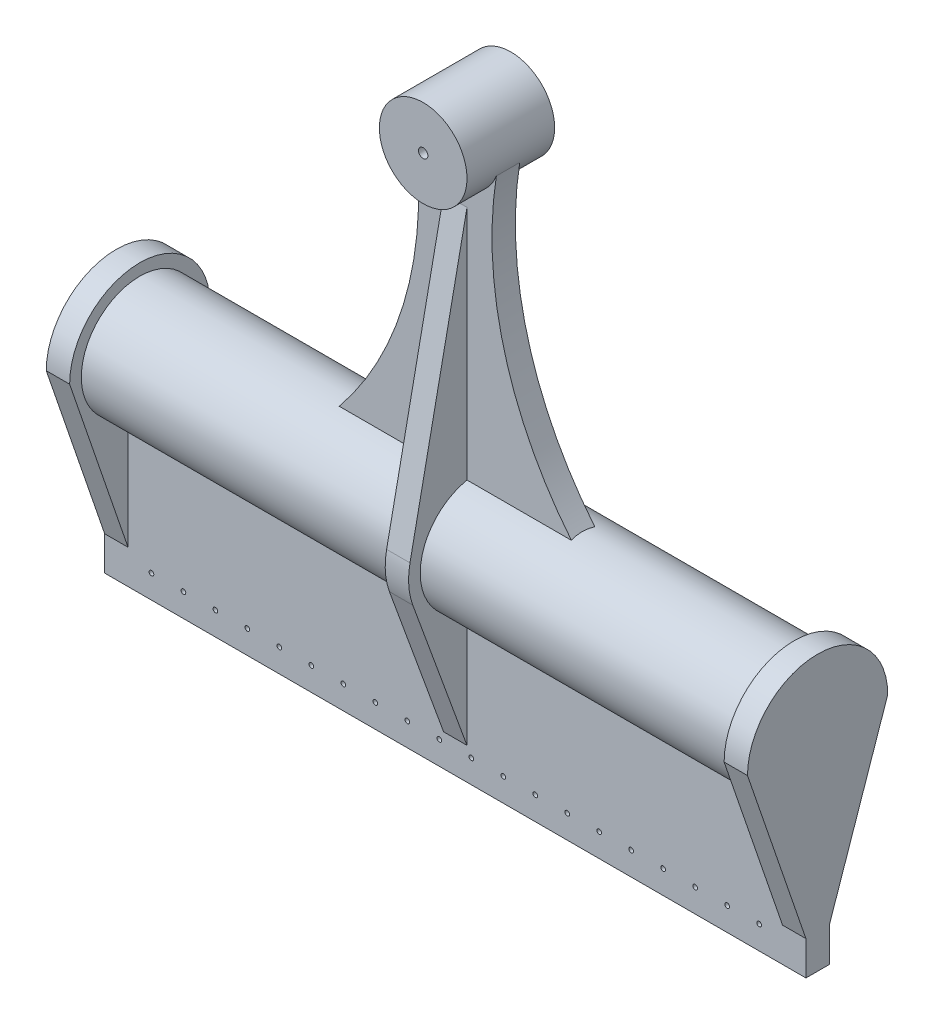
SolidWorks part; units mm, degrees
ref_plane "Front Plane" through (0, 0, 0) normal (1, 0, 0) x (0, 1, 0)
ref_plane "Top Plane" through (0, 0, 0) normal (0, 0, 1) x (0, 1, 0)
ref_plane "Right Plane" through (0, 0, 0) normal (0, 1, 0) x (-1, 0, 0)
sketch "Coefficients Plate Sketch" plane through (0, 0, 0) normal (0, 0, 1) x (0, 1, 0)
  line L1 (-44.45, -76.2) -> (0, -76.2)
  line L2 (-44.45, -76.2) -> (-44.45, 76.2)
  line L3 (-44.45, 76.2) -> (0, 76.2)
  line L4 (0, -76.2) -> (0, 76.2)
  line L5 (-44.45, -76.2) -> (0, 76.2) construction
  line L6 (-44.45, 76.2) -> (0, -76.2) construction
  circle A0 centre (-39.37, -66.04) radius 0.508
  circle A1 centre (-39.37, -59.0884) radius 0.508
  circle A2 centre (-39.37, -52.1368) radius 0.508
  circle A3 centre (-39.37, -45.1853) radius 0.508
  circle A4 centre (-39.37, -38.2337) radius 0.508
  circle A5 centre (-39.37, -31.2821) radius 0.508
  circle A6 centre (-39.37, -24.3305) radius 0.508
  circle A7 centre (-39.37, -17.3789) radius 0.508
  circle A8 centre (-39.37, -10.4274) radius 0.508
  circle A9 centre (-39.37, -3.4758) radius 0.508
  circle A10 centre (-39.37, 3.4758) radius 0.508
  circle A11 centre (-39.37, 10.4274) radius 0.508
  circle A12 centre (-39.37, 17.3789) radius 0.508
  circle A13 centre (-39.37, 24.3305) radius 0.508
  circle A14 centre (-39.37, 31.2821) radius 0.508
  circle A15 centre (-39.37, 38.2337) radius 0.508
  circle A16 centre (-39.37, 45.1853) radius 0.508
  circle A17 centre (-39.37, 52.1368) radius 0.508
  circle A18 centre (-39.37, 59.0884) radius 0.508
  circle A19 centre (-39.37, 66.04) radius 0.508
  point P0 (-22.225, 0)
  point P45 (0, 0)
  dimension "D2" = 1.016
  dimension "D3" = 22.225
  dimension "D4" = 39.37
  dimension "D5" = 3.4758
  dimension "D6" = 10.4274
  dimension "D7" = 76.2
  dimension "D1" = 20
extrude "Coefficients Plate" add sketch "Coefficients Plate Sketch" along normal blind 2.54 and the other way blind 2.54
sketch "Pivot Cylinder Sketch" plane through (0, 0, 0) normal (1, 0, 0) x (0, 1, 0)
  circle A0 centre (0, 0) radius 12.7
  dimension "D1" = 25.4
extrude "Pivot Cylinder" add sketch "Pivot Cylinder Sketch" along normal blind 76.2 and the other way blind 76.2
sketch "Edge Rib Front Sketch" plane through (0, 0, 0) normal (1, 0, 0) x (0, 1, 0)
  line L0 (0, 15.24) -> (-44.45, 0)
  line L1 (-44.45, 0) -> (0, -15.24)
  arc A0 (0, -15.24) -> (0, 15.24) centre (0, 0) ccw
extrude "Edge Rib Front" add sketch "Edge Rib Front Sketch" along normal blind 5.08 from offset 71.12
sketch "Edge Rib Back Sketch" plane through (0, 0, 0) normal (1, 0, 0) x (0, 1, 0)
  line L0 (0, 15.24) -> (-44.45, 0)
  line L1 (-44.45, 0) -> (0, -15.24)
  arc A0 (0, -15.24) -> (0, 15.24) centre (0, 0) ccw
extrude "Edge Rib Back" add sketch "Edge Rib Back Sketch" against normal blind 5.08 from offset 71.12 offset against normal yes
sketch "Summation Plate Sketch" plane through (0, 0, 0) normal (0, 0, 1) x (0, 1, 0)
  line L0 (0, -38.1) -> (0, 38.1)
  line L1 (76.2, 9.525) -> (76.2, -9.525)
  arc A0 (0, 38.1) -> (76.2, 9.525) centre (60.8501, 84.4794) ccw
  arc A1 (76.2, -9.525) -> (0, -38.1) centre (60.8501, -84.4794) ccw
extrude "Summation Plate" add sketch "Summation Plate Sketch" along normal blind 2.54 and the other way blind 2.54
sketch "Summation Anchor Sketch" plane through (0, 0, 0) normal (0, 0, 1) x (0, 1, 0)
  circle A0 centre (76.2, 0) radius 9.525
  circle A1 centre (76.2, 0) radius 1.016
extrude "Summation Anchor" add sketch "Summation Anchor Sketch" along normal blind 9.525 and the other way blind 9.525
sketch "Middle Rib Sketch" plane through (0, 0, 0) normal (1, 0, 0) x (0, 1, 0)
  line L0 (-44.45, 0) -> (-5.225, 14.3163)
  line L1 (-44.45, -2.54) -> (-44.45, 2.54) construction
  line L2 (3.0481, 14.9321) -> (76.2, 0)
  line L3 (76.2, 0) -> (3.0481, -14.9321)
  line L4 (-5.225, -14.3163) -> (-44.45, 0)
  line L5 (-44.45, 0) -> (76.2, 0) construction
  arc A0 (-5.225, 14.3163) -> (3.0481, 14.9321) centre (0.0001, 0) cw
  arc A1 (0, -15.24) -> (0, 15.24) centre (0, 0) ccw construction
  arc A2 (3.0481, -14.9321) -> (-5.225, -14.3163) centre (0.0001, 0) cw
extrude "Middle Rib" add sketch "Middle Rib Sketch" along normal blind 2.54 and the other way blind 2.54
